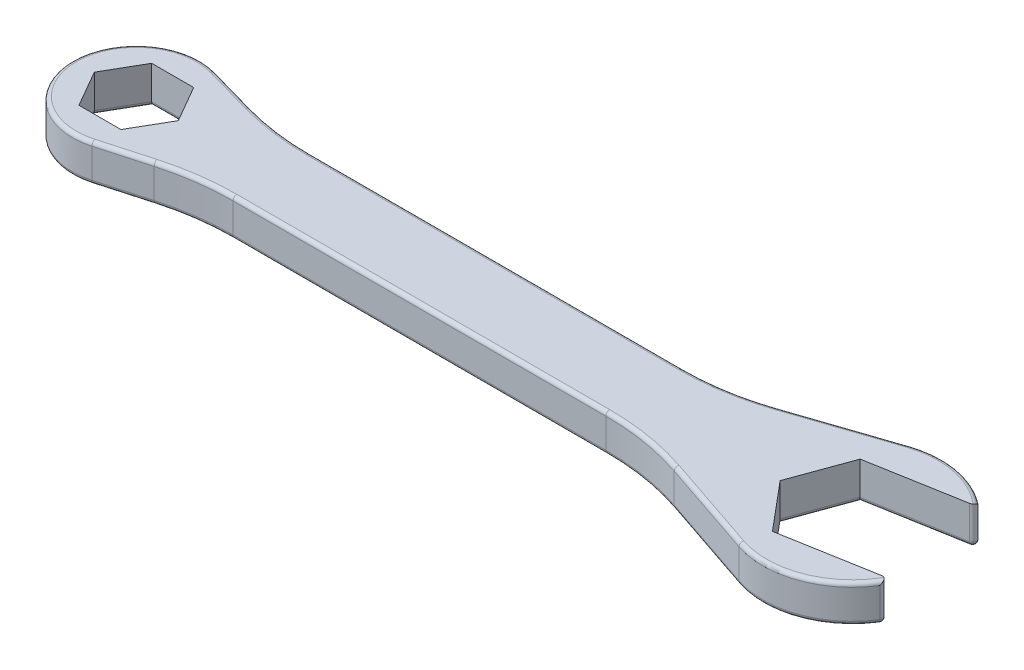
SolidWorks part; units mm, degrees
ref_plane "Alzado" through (0, 0, 0) normal (0, 0, 1) x (1, 0, 0)
ref_plane "Planta" through (0, 0, 0) normal (0, 1, 0) x (1, 0, 0)
ref_plane "Vista lateral" through (0, 0, 0) normal (1, 0, 0) x (0, 0, -1)
sketch "Croquis1" plane through (0, 0, 0) normal (0, 1, 0) x (1, 0, 0)
  line L0 (181.1187, -40.5038) -> (257.6132, -66.3237)
  line L1 (-150, -30) -> (117.1563, -30)
  line L3 (-150, 30) -> (117.1563, 30)
  line L7 (181.1187, 40.5038) -> (257.6132, 66.3237)
  line L8 (-266.4662, -48.1335) -> (-228.5265, -37.4659)
  line L9 (-174.3912, -30) -> (-150, -30)
  line L10 (-266.4662, 48.1335) -> (-228.5265, 37.4659)
  line L11 (-174.3912, 30) -> (-150, 30)
  arc A0 (257.6132, -66.3237) -> (257.6132, 66.3237) centre (280, 0) ccw
  arc A1 (-266.4662, 48.1335) -> (-266.4662, -48.1335) centre (-280, 0) ccw
  arc A2 (-228.5265, 37.4659) -> (-174.3912, 30) centre (-174.3912, 230) ccw
  arc A3 (-228.5265, -37.4659) -> (-174.3912, -30) centre (-174.3912, -230) cw
  arc A4 (117.1563, -30) -> (181.1187, -40.5038) centre (117.1563, -230) cw
  arc A5 (117.1563, 30) -> (181.1187, 40.5038) centre (117.1563, 230) ccw
  point P0 (0, 0)
  dimension "D1" = 280
  dimension "D2" = 280
  dimension "D3" = 200
extrude "Saliente-Extruir1" add sketch "Croquis1" along normal blind 29
sketch "Croquis2" plane through (0, 0, 0) normal (0, 1, 0) x (1, 0, 0)
  line L1 (-312.8482, 0) -> (-296.4241, -28.4474)
  line L2 (-296.4241, -28.4474) -> (-263.5759, -28.4474)
  line L3 (-263.5759, -28.4474) -> (-247.1518, 0)
  line L4 (-247.1518, 0) -> (-263.5759, 28.4474)
  line L5 (-263.5759, 28.4474) -> (-296.4241, 28.4474)
  line L6 (-296.4241, 28.4474) -> (-312.8482, 0)
  line L8 (296.6938, 45.866) -> (248.6258, 37.3903)
  line L9 (248.6258, 37.3903) -> (231.932, -8.4757)
  line L10 (231.932, -8.4757) -> (263.3062, -45.866)
  line L11 (263.3062, -45.866) -> (311.3742, -37.3903)
  line L13 (296.6938, 45.866) -> (378.6704, 60.3207)
  line L14 (311.3742, -37.3903) -> (393.3507, -22.9356)
  line L15 (378.6704, 60.3207) -> (393.3507, -22.9356)
  line L16 (311.3742, -37.3903) -> (328.068, 8.4757) [skipped]
  line L17 (328.068, 8.4757) -> (296.6938, 45.866) [skipped]
extrude "Cortar-Extruir1" cut sketch "Croquis2" along normal blind 46
sketch "Croquis3" plane through (0, 0, 0) normal (0, 1, 0) x (1, 0, 0)
  line L0 (-149.5659, 0) -> (149.5659, 0) construction
  line L1 (-149.5659, 14.0046) -> (149.5659, 14.0046)
  line L2 (-149.5659, -14.0046) -> (149.5659, -14.0046)
  arc A0 (-149.5659, 14.0046) -> (-149.5659, -14.0046) centre (-149.5659, 0) ccw
  arc A1 (149.5659, -14.0046) -> (149.5659, 14.0046) centre (149.5659, 0) ccw
  point P2 (0, 0)
extrude "Saliente-Extruir2" add sketch "Croquis3" against normal blind 5
sketch "Croquis4" plane through (0, 0, 0) normal (0, 1, 0) x (1, 0, 0)
  line L0 (-163.5705, 0) -> (163.5705, 0) construction
  arc A0 (-149.5659, 14.0046) -> (-149.5659, -14.0046) centre (-149.5659, 0) ccw construction
  arc A1 (149.5659, -14.0046) -> (149.5659, 14.0046) centre (149.5659, 0) ccw construction
  text T0 "1/8      Ingenieria Fotonica 2018       15" font "Century Gothic" height 3.5
extrude "Cortar-Extruir2" cut sketch "Croquis4" against normal blind 38
fillet "Redondeo2" radius 3 42 edges at (294.6742, 29, -68.4446) (219.366, 29, -53.4137) (149.5659, 29, -32.6434) (-28.6174, 29, -30) (-201.7151, 29, -31.8753) (-247.4963, 29, -42.7997) (-330, 29, 0) (-247.4963, 29, 42.7997) (-201.7151, 29, 31.8753) (306.3365, 29, 64.8567) (219.366, 29, 53.4137) (149.5659, 29, 32.6434) (-255.3639, 0, -14.2237) (-255.3639, 0, 14.2237) (-280, 0, 28.4474) (-304.6361, 0, 14.2237) (-304.6361, 0, -14.2237) (-280, 0, -28.4474) (219.366, 0, -53.4137) (149.5659, 0, -32.6434) (-28.6174, 0, -30) (-201.7151, 0, -31.8753) (-247.4963, 0, -42.7997) (-330, 0, 0) (-247.4963, 0, 42.7997) (-201.7151, 0, 31.8753) (-28.6174, 0, 30) (149.5659, 0, 32.6434) (219.366, 0, 53.4137) (306.3365, 0, 64.8567) (302.7974, 0, 38.9026) (247.6191, 0, 27.1708) (240.2789, 0, -14.4573) (288.1171, 0, -44.3537) (294.6742, 0, -68.4446) (0, 0, -14.0046) (163.5705, 0, 0) (0, 0, 14.0046) (-163.5705, 0, 0) (327.6084, 14.5, -51.317) (342.2887, 14.5, 31.9392) (-28.6174, 29, 30)
